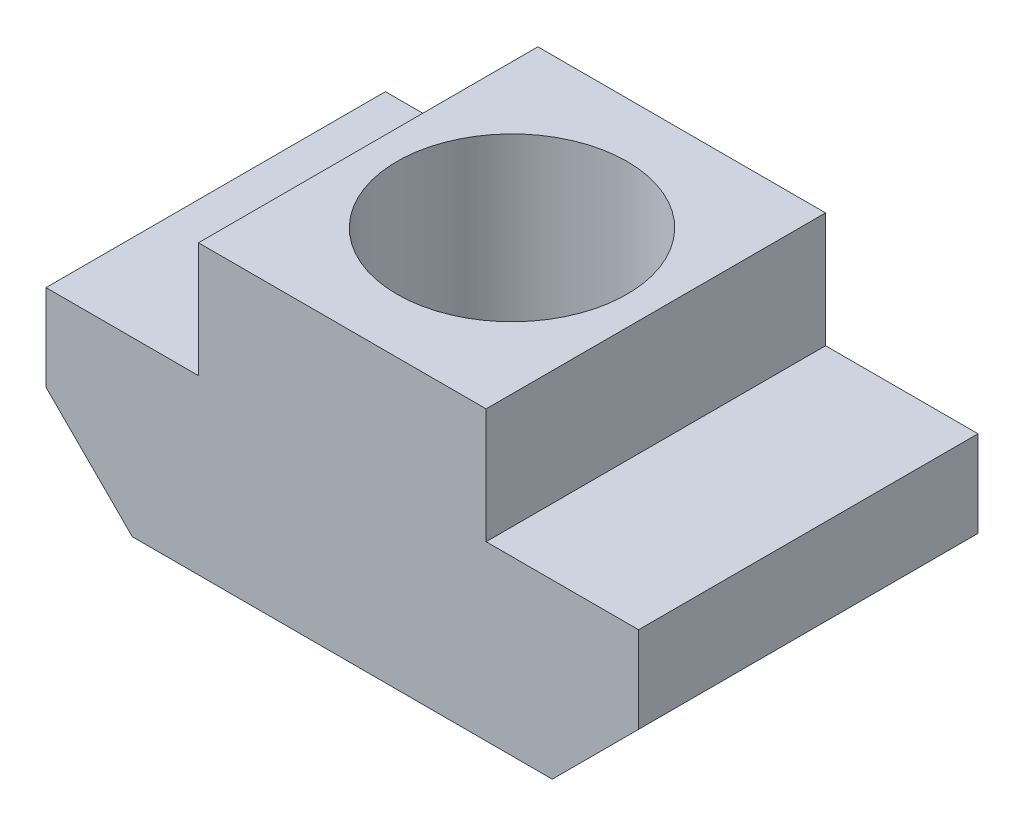
SolidWorks part; units mm, degrees
ref_plane "前视基准面" through (0, 0, 0) normal (0, 0, 1) x (1, 0, 0)
ref_plane "上视基准面" through (0, 0, 0) normal (0, 1, 0) x (1, 0, 0)
ref_plane "右视基准面" through (0, 0, 0) normal (1, 0, 0) x (0, 0, -1)
sketch "草图1" plane through (0, 0, 0) normal (0, 1, 0) x (1, 0, 0)
  line L1 (5.15, 2.95) -> (-5.15, 2.95)
  line L2 (5.15, 2.95) -> (5.15, -2.95)
  line L3 (5.15, -2.95) -> (-5.15, -2.95)
  line L4 (-5.15, 2.95) -> (-5.15, -2.95)
  line L5 (2.5, 2.95) -> (-2.5, 2.95)
  line L6 (2.5, 2.95) -> (2.5, -2.95)
  line L7 (2.5, -2.95) -> (-2.5, -2.95)
  line L8 (-2.5, 2.95) -> (-2.5, -2.95)
  line L9 (2.5, 2.95) -> (-2.5, -2.95) construction
  line L10 (2.5, -2.95) -> (-2.5, 2.95) construction
  circle A0 centre (0, 0) radius 2
  point P0 (0, 0)
  dimension "D3" = 5.9
  dimension "D1" = 10.3
  dimension "D2" = 5.9
  dimension "D4" = 5
extrude "凸台-拉伸3" add sketch "草图1" along normal blind 3 contours L8 L1 L4 L3 | L1 L6 L3 L2 region at (3.825, 0, 0) region at (-3.825, 0, 0)
extrude "凸台-拉伸4" add sketch "草图1<3>" along normal blind 5 contours L1 L8 L3 L6 A0 region at (2.4227, 0, 0)
sketch "草图1<3>" plane through (0, 0, 0) normal (0, 1, 0) x (1, 0, 0) same geometry as "草图1"
sketch "草图2" plane through (0, 0, 2.95) normal (0, 0, 1) x (1, 0, 0)
  line L0 (-5.15, 3) -> (-5.15, 0) construction
  line L1 (-5.15, 1.5) -> (-3.65, 0)
  line L2 (5.15, 0) -> (-5.15, 0) construction
  line L3 (5.15, 1.5) -> (3.65, 0)
  line L4 (5.15, 3) -> (5.15, 0) construction
  line L5 (3.65, 0) -> (5.15, 0)
  line L6 (5.15, 0) -> (5.15, 1.5)
  line L7 (-3.65, 0) -> (-5.15, 0)
  line L8 (-5.15, 0) -> (-5.15, 1.5)
extrude "切除-拉伸1" cut sketch "草图2" against normal through all
